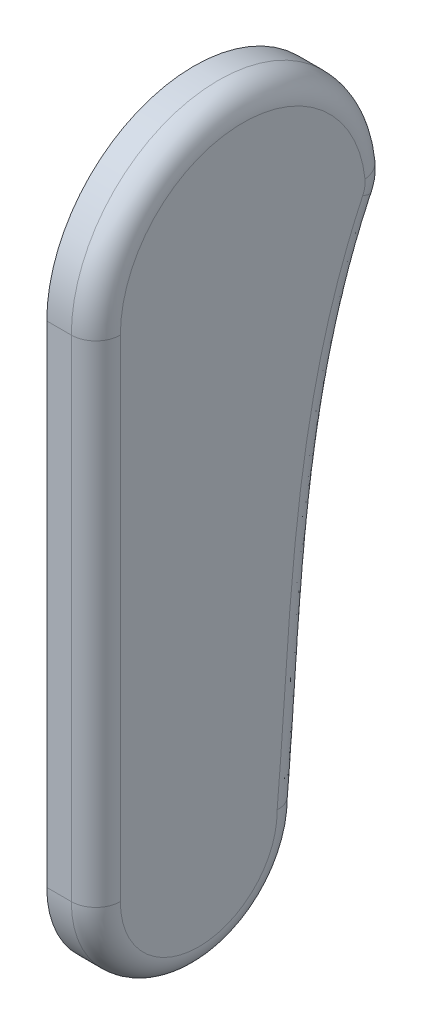
SolidWorks part; units mm, degrees
ref_plane "Front Plane" through (0, 0, 0) normal (0, 0, 1) x (1, 0, 0)
ref_plane "Top Plane" through (0, 0, 0) normal (0, 1, 0) x (1, 0, 0)
ref_plane "Right Plane" through (0, 0, 0) normal (1, 0, 0) x (0, 0, -1)
sketch "Sketch2" plane through (0, 0, 0) normal (1, 0, 0) x (0, 0, -1)
  line L2 (-30, 50) -> (-30, -50)
  arc A0 (-30, 50) -> (29.8379, 53.1141) centre (0, 50) cw
  arc A1 (29.8379, 53.1141) -> (28.9342, 47.8054) centre (19.892, 52.076) cw
  arc A2 (-30, -50) -> (11.9583, -50) centre (-9.0209, -50) ccw
  spline S0 degree 3 poles (28.9342, 47.8054) (24.8825, 39.2268) (14.6324, 7.562) (14.0777, -26.4513) (11.9583, -50) knots 0.023515 0.023515 0.023515 0.023515 0.298368 1 1 1 1
extrude "Boss-Extrude1" add sketch "Sketch2" along normal blind 10
fillet "Fillet1" radius 5 5 edges at (10, -70.9791, 9.0209) (10, 0, 30) (10, 79.9595, 1.5591) (10, 50.3978, -29.7501)
sketch "Sketch6" plane through (0, 0, 0) normal (-1, 0, 0) x (0, 0, 1)
  circle A1 centre (-3.5419, 59.3749) radius 2.25
  circle A2 centre (3.5227, 40.6642) radius 2.25
  circle A3 centre (-0.0096, 50.0196) radius 1.3762
extrude "Cut-Extrude3" cut sketch "Sketch6" against normal blind 0.5
